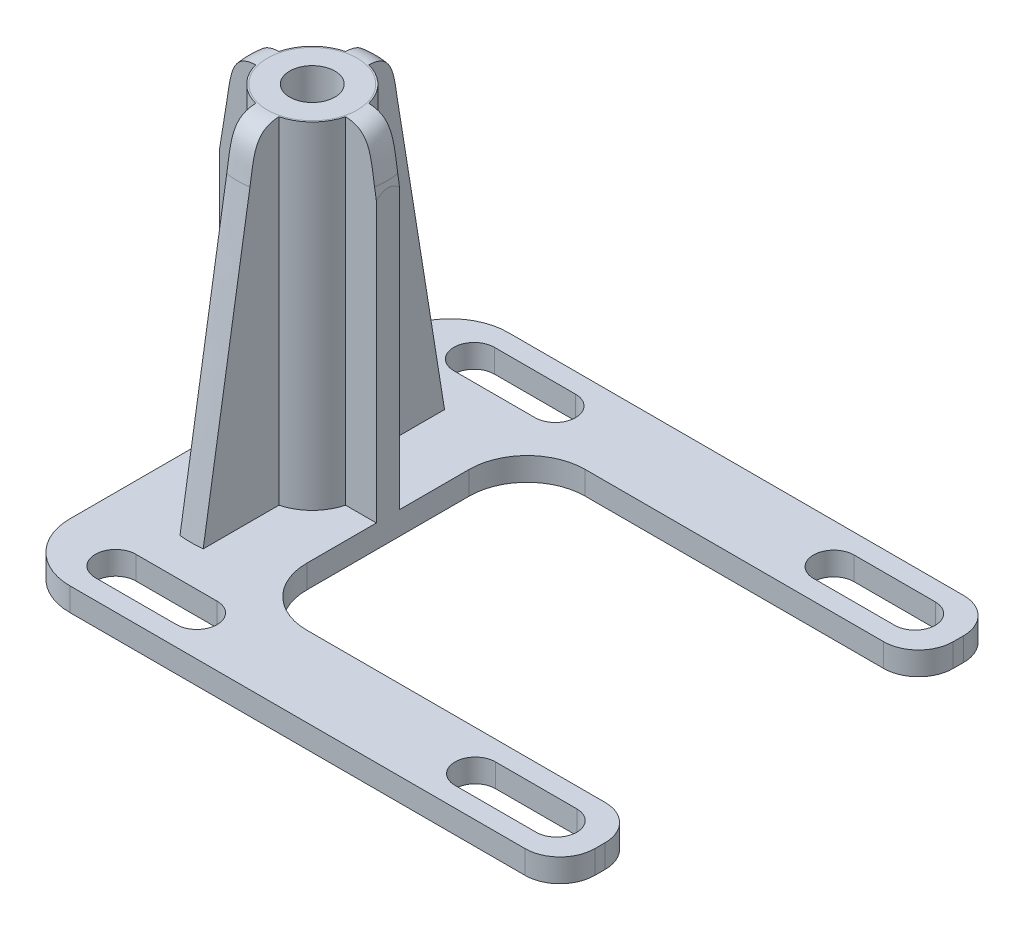
SolidWorks part; units mm, degrees
ref_plane "Front Plane" through (0, 0, 0) normal (0, 0, 1) x (1, 0, 0)
ref_plane "Top Plane" through (0, 0, 0) normal (0, 1, 0) x (1, 0, 0)
ref_plane "Right Plane" through (0, 0, 0) normal (1, 0, 0) x (0, 0, -1)
sketch "Sketch1" plane through (0, 0, 0) normal (0, 1, 0) x (1, 0, 0)
  line L0 (47.2433, 30.9) -> (47.2433, 37.8)
  line L1 (47.2433, 6.9) -> (13.5188, 6.9)
  line L3 (47.2433, 30.9) -> (13.5188, 30.9)
  line L4 (13.5188, 6.9) -> (13.5188, 30.9)
  line L5 (5.4933, 34.35) -> (12.4933, 34.35) construction
  line L6 (5.4933, 36.1) -> (12.4933, 36.1)
  line L7 (47.2433, 0) -> (0, 0)
  line L9 (47.2433, 37.8) -> (0, 37.8)
  line L10 (0, 0) -> (0, 37.8)
  line L11 (5.4933, 32.6) -> (12.4933, 32.6)
  line L12 (36.4933, 34.35) -> (43.4933, 34.35) construction
  line L13 (47.2433, 6.9) -> (47.2433, 0)
  line L14 (36.4933, 36.1) -> (43.4933, 36.1)
  line L15 (36.4933, 32.6) -> (43.4933, 32.6)
  line L16 (5.4933, 3.45) -> (12.4933, 3.45) construction
  line L17 (5.4933, 5.2) -> (12.4933, 5.2)
  line L18 (5.4933, 1.7) -> (12.4933, 1.7)
  line L19 (36.4933, 3.45) -> (43.4933, 3.45) construction
  line L20 (36.4933, 5.2) -> (43.4933, 5.2)
  line L21 (36.4933, 1.7) -> (43.4933, 1.7)
  line L22 (8.9933, 34.35) -> (39.9933, 3.45) construction
  line L23 (39.9933, 34.35) -> (8.9933, 3.45) construction
  arc A0 (5.4933, 36.1) -> (5.4933, 32.6) centre (5.4933, 34.35) ccw
  arc A1 (12.4933, 32.6) -> (12.4933, 36.1) centre (12.4933, 34.35) ccw
  arc A2 (36.4933, 36.1) -> (36.4933, 32.6) centre (36.4933, 34.35) ccw
  arc A3 (43.4933, 32.6) -> (43.4933, 36.1) centre (43.4933, 34.35) ccw
  arc A4 (5.4933, 5.2) -> (5.4933, 1.7) centre (5.4933, 3.45) ccw
  arc A5 (12.4933, 1.7) -> (12.4933, 5.2) centre (12.4933, 3.45) ccw
  arc A6 (36.4933, 5.2) -> (36.4933, 1.7) centre (36.4933, 3.45) ccw
  arc A7 (43.4933, 1.7) -> (43.4933, 5.2) centre (43.4933, 3.45) ccw
  point P0 (0, 0)
  point P6 (0, 0)
  point P8 (8.9933, 34.35)
  point P18 (39.9933, 34.35)
  point P25 (8.9933, 3.45)
  point P32 (39.9933, 3.45)
  point P39 (47.2433, 34.35)
  point P40 (47.2433, 3.45)
  point P43 (45.2433, 34.35)
  dimension "D3" = 1.75
  dimension "D1" = 6.9
  dimension "D2" = 7
  dimension "D4" = 38
  dimension "D5" = 2
  dimension "D6" = 30.9
extrude "Boss-Extrude1" add sketch "Sketch1" along normal blind 2
fillet "Fillet1" radius 5 4 edges at (0, 1, -37.8) (0, 1, 0) (13.5188, 1, -6.9) (13.5188, 1, -30.9)
fillet "Fillet2" radius 3 4 edges at (47.2433, 1, -6.9) (47.2433, 1, 0) (47.2433, 1, -30.9) (47.2433, 1, -37.8)
sketch "Sketch2" plane through (0, 2, 0) normal (0, 1, 0) x (1, 0, 0)
  line L0 (0, 32.8) -> (0, 5) construction
  line L1 (13.5188, 11.9) -> (13.5188, 25.9) construction
  line L2 (12.4933, 6.9) -> (36.4933, 6.9) construction
  line L3 (12.4933, 6.9) -> (12.4933, 30.9) construction
  line L4 (12.4933, 30.9) -> (36.4933, 30.9) construction
  line L5 (36.4933, 6.9) -> (36.4933, 30.9) construction
  line L6 (12.4933, 6.9) -> (36.4933, 30.9) construction
  line L7 (12.4933, 30.9) -> (36.4933, 6.9) construction
  line L9 (5.9933, 22.773) -> (5.9933, 29.35)
  line L10 (5.9933, 29.35) -> (7.9933, 29.35)
  line L11 (7.9933, 22.773) -> (7.9933, 29.35)
  line L13 (5.9933, 15.027) -> (5.9933, 8.45)
  line L14 (5.9933, 8.45) -> (7.9933, 8.45)
  line L15 (7.9933, 15.027) -> (7.9933, 8.45)
  line L16 (10.8663, 19.9) -> (13.5188, 19.9)
  line L18 (10.8663, 17.9) -> (13.5188, 17.9)
  line L19 (13.5188, 19.9) -> (13.5188, 17.9)
  line L21 (3.1203, 19.9) -> (0, 19.9)
  line L23 (3.1203, 17.9) -> (0, 17.9)
  line L24 (0, 19.9) -> (0, 17.9)
  arc A0 (5.9933, 22.773) -> (3.1203, 19.9) centre (6.9933, 18.9) ccw
  circle A1 centre (6.9933, 18.9) radius 1.95
  arc A2 (5.4933, 36.1) -> (5.4933, 32.6) centre (5.4933, 34.35) ccw construction
  arc A3 (5.4933, 5.2) -> (5.4933, 1.7) centre (5.4933, 3.45) ccw construction
  arc A4 (7.9933, 15.027) -> (10.8663, 17.9) centre (6.9933, 18.9) ccw
  arc A5 (3.1203, 17.9) -> (5.9933, 15.027) centre (6.9933, 18.9) ccw
  arc A6 (10.8663, 19.9) -> (7.9933, 22.773) centre (6.9933, 18.9) ccw
  point P6 (0, 18.9)
  point P7 (24.4933, 18.9)
  point P24 (3.7433, 34.35)
  point P28 (3.7433, 3.45)
  dimension "D1" = 3.9
  dimension "D2" = 8
  dimension "D3" = 24
  dimension "D4" = 24
  dimension "D5" = 17.5
  dimension "D6" = 5
  dimension "D7" = 5
  dimension "D8" = 2
  dimension "D9" = 2
  dimension "D10" = 2
  dimension "D11" = 2
extrude "Boss-Extrude2" add sketch "Sketch2" along normal blind 29
ref_plane "Plane1" through (6.9933, 0, 0) normal (-1, 0, 0) x (0, 0, 1)
sketch "Sketch4" plane through (6.9933, 0, 0) normal (-1, 0, 0) x (0, 0, 1)
  line L0 (-8.45, 2) -> (-12.45, 27)
  line L7 (-15.027, 31) -> (-8.45, 31) construction
  line L8 (-8.45, 2) -> (-6.9, 2)
  line L9 (-6.9, 2) -> (-6.9, 31)
  line L10 (-6.9, 31) -> (-15.027, 31)
  line L11 (-18.9, 0) -> (-18.9, 31) construction
  line L12 (-32.8, 0) -> (-5, 0) construction
  line L13 (-19.9, 31) -> (-17.9, 31) construction
  spline S0 degree 3 poles (-12.45, 27) (-12.7906, 29.1288) (-12.8032, 31) (-15.027, 31) knots 0 0 0 0 1 1 1 1
  dimension "D1" = 25
  dimension "D2" = 4
revolve "Cut-Revolve3" cut sketch "Sketch4" angle 360 about L11
